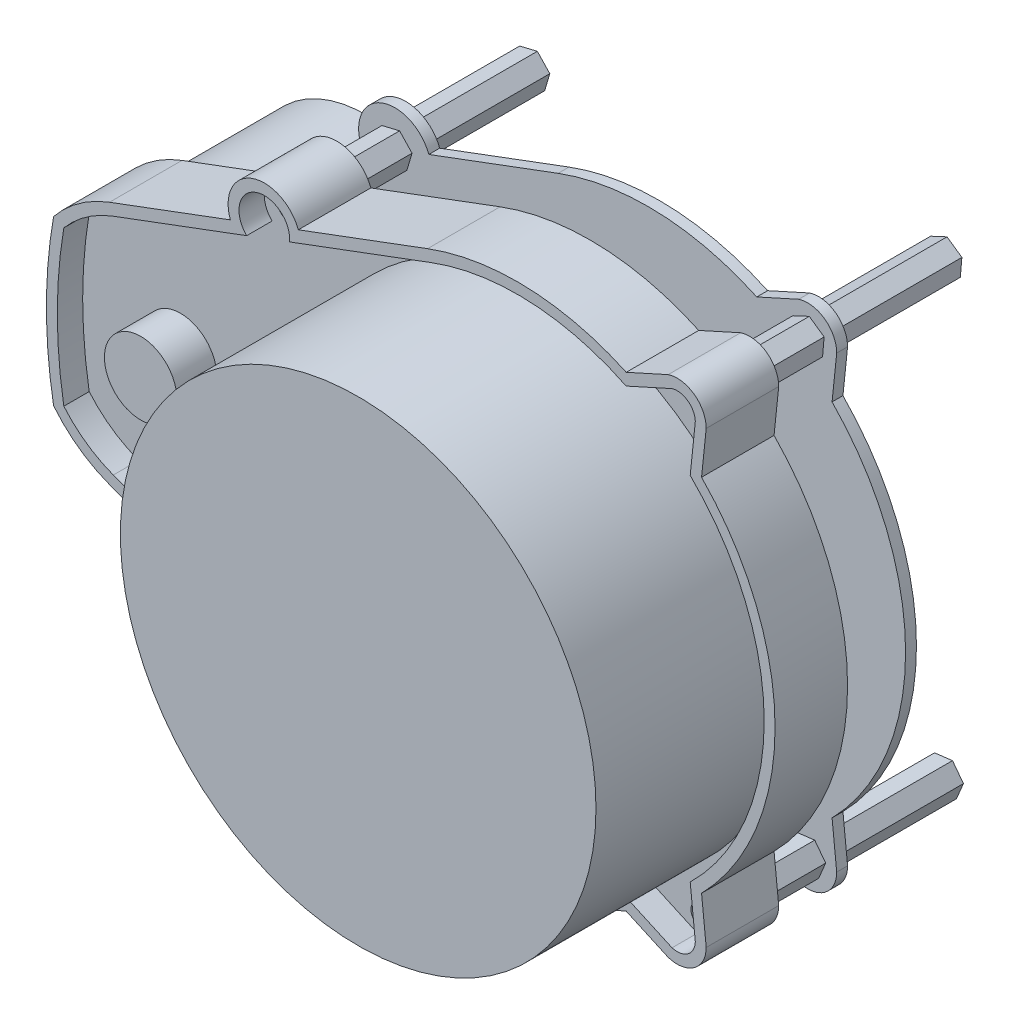
SolidWorks part; units mm, degrees
ref_plane "Plan de face" through (0, 0, 0) normal (0, 0, 1) x (1, 0, 0)
ref_plane "Plan de dessus" through (0, 0, 0) normal (0, 1, 0) x (1, 0, 0)
ref_plane "Plan de droite" through (0, 0, 0) normal (1, 0, 0) x (0, 0, -1)
sketch "Esquisse1" plane through (0, 0, 0) normal (0, 0, 1) x (1, 0, 0)
  line L0 (-12.425, 33.2546) -> (-30.2572, 26.5919)
  line L1 (-56.3, 16.8615) -> (-56.3, -16.8615) construction
  line L2 (-50, 0) -> (0, 0) construction
  line L3 (-12.425, 33.2546) -> (-12.425, -33.2546) construction
  line L5 (-35, 25) -> (-34.9409, 24.8419) construction
  line L6 (-39.6247, 23.0919) -> (-56.3, 16.8615)
  line L7 (-33.4505, 25.3988) -> (-36.4314, 24.2851)
  line L8 (20.756, 34.8016) -> (14.974, 32.1874)
  line L9 (26, 31) -> (25.36, 24.8419)
  line L10 (-65, 0) -> (35.5, 0) construction
  line L11 (55, 0) -> (-55, 0) construction
  line L12 (-35, -25) -> (-34.9409, -24.8419) construction
  line L13 (26, -31) -> (25.36, -24.8419)
  line L14 (20.756, -34.8016) -> (14.974, -32.1874)
  line L15 (-33.4505, -25.3988) -> (-36.4314, -24.2851)
  line L16 (-39.6247, -23.0919) -> (-56.3, -16.8615)
  line L17 (-12.425, -33.2546) -> (-30.2572, -26.5919)
  arc A1 (25.36, -24.8419) -> (25.36, 24.8419) centre (0, 0) ccw
  arc A3 (-64.01, 11.3013) -> (-64.01, -11.3013) centre (0, 0) ccw
  arc A4 (-56.3, 16.8615) -> (-64.01, 11.3013) centre (-50, 0) ccw
  circle A5 centre (22, 31) radius 1.6
  circle A6 centre (-35, 25) radius 1.6
  arc A7 (-30.2572, 26.5919) -> (-39.6247, 23.0919) centre (-34.9409, 24.8419) ccw
  arc A8 (26, 31) -> (20.756, 34.8016) centre (22, 31) ccw
  arc A9 (14.974, 32.1874) -> (-12.425, 33.2546) centre (0, 0) ccw
  arc A10 (14.974, -32.1874) -> (-12.425, -33.2546) centre (0, 0) cw
  arc A11 (26, -31) -> (20.756, -34.8016) centre (22, -31) cw
  arc A12 (-30.2572, -26.5919) -> (-39.6247, -23.0919) centre (-34.9409, -24.8419) cw
  circle A13 centre (-35, -25) radius 1.6
  circle A14 centre (22, -31) radius 1.6
  arc A15 (-56.3, -16.8615) -> (-64.01, -11.3013) centre (-50, 0) cw
  point P28 (-12.425, 0)
  point P29 (-56.3, 0)
  dimension "D1" = 71
  dimension "D4" = 130
  dimension "D6" = 3.2
  dimension "D10" = 10
  dimension "D11" = 8
  dimension "D3" = 50
  dimension "D5" = 31
  dimension "D7" = 22
  dimension "D8" = 35
  dimension "D9" = 25
extrude "Boss.-Extru.1" add sketch "Esquisse1" along normal blind 10 contours A15 L16 A12 L17 A10 L14 A11 L13 A1 L9 A8 L8 A9 L0 A7 L6 A4 A3 A13 A5 A6 A14 region at (-11.1105, 0, 0)
sketch "Esquisse2" plane through (0, 0, 10) normal (0, 0, 1) x (1, 0, 0)
  circle A0 centre (0, 0) radius 32.8
  dimension "D1" = 65.6
extrude "Boss.-Extru.2" add sketch "Esquisse2" along normal blind 22
sketch "Esquisse3" plane through (0, 0, 10) normal (0, 0, 1) x (1, 0, 0)
  line L16 (-55.775, -15.4564) -> (-37.3782, -22.33)
  line L17 (14.9568, -30.5335) -> (21.2911, -33.3974)
  line L18 (24.4991, -31.0687) -> (23.7942, -24.2866)
  line L19 (23.7942, 24.2866) -> (24.4991, 31.0687)
  line L20 (21.2911, 33.3974) -> (14.9568, 30.5335)
  line L21 (-11.9, 31.8495) -> (-31.4537, 24.5436)
  line L22 (-55.775, -15.4564) -> (-37.3782, -22.33)
  line L23 (14.9568, -30.5335) -> (21.2911, -33.3974)
  line L24 (24.4991, -31.0687) -> (23.7942, -24.2866)
  line L25 (23.7942, 24.2866) -> (24.4991, 31.0687)
  line L26 (21.2911, 33.3974) -> (14.9568, 30.5335)
  line L27 (-11.9, 31.8495) -> (-31.4537, 24.5436)
  line L28 (-31.4537, -24.5436) -> (-11.9, -31.8495)
  line L29 (-31.4537, -24.5436) -> (-11.9, -31.8495)
  line L30 (-37.3782, 22.33) -> (-55.775, 15.4564)
  line L31 (-37.3782, 22.33) -> (-55.775, 15.4564)
  arc A20 (-62.6, -10.6532) -> (-55.775, -15.4564) centre (-50, 0) ccw
  arc A21 (-11.9, -31.8495) -> (14.9568, -30.5335) centre (0, 0) ccw
  arc A22 (23.7942, -24.2866) -> (23.7942, 24.2866) centre (0, 0) ccw
  arc A23 (14.9568, 30.5335) -> (-11.9, 31.8495) centre (0, 0) ccw
  arc A24 (-55.775, 15.4564) -> (-62.6, 10.6532) centre (-50, 0) ccw
  arc A25 (-62.6, 10.6532) -> (-62.6, -10.6532) centre (0, 0) ccw
  arc A26 (-62.6, -10.6532) -> (-55.775, -15.4564) centre (-50, 0) ccw
  arc A27 (-11.9, -31.8495) -> (14.9568, -30.5335) centre (0, 0) ccw
  arc A28 (23.7942, -24.2866) -> (23.7942, 24.2866) centre (0, 0) ccw
  arc A29 (14.9568, 30.5335) -> (-11.9, 31.8495) centre (0, 0) ccw
  arc A30 (-55.775, 15.4564) -> (-62.6, 10.6532) centre (-50, 0) ccw
  arc A31 (-62.6, 10.6532) -> (-62.6, -10.6532) centre (0, 0) ccw
  arc A32 (-37.3782, -22.33) -> (-31.4537, -24.5436) centre (-34.9409, -24.8419) ccw
  arc A33 (-37.3782, -22.33) -> (-31.4537, -24.5436) centre (-34.9409, -24.8419) ccw
  arc A34 (21.2911, -33.3974) -> (24.4991, -31.0687) centre (22, -31) ccw
  arc A35 (21.2911, -33.3974) -> (24.4991, -31.0687) centre (22, -31) ccw
  arc A36 (24.4991, 31.0687) -> (21.2911, 33.3974) centre (22, 31) ccw
  arc A37 (24.4991, 31.0687) -> (21.2911, 33.3974) centre (22, 31) ccw
  arc A38 (-31.4537, 24.5436) -> (-37.3782, 22.33) centre (-34.9409, 24.8419) ccw
  arc A39 (-31.4537, 24.5436) -> (-37.3782, 22.33) centre (-34.9409, 24.8419) ccw
  dimension "D1" = 1.5
extrude "Enlèv. mat.-Extru.1" cut sketch "Esquisse3" against normal blind 3.5
sketch "Esquisse4" plane through (0, 0, 10) normal (0, 0, -1) x (-1, 0, 0)
  circle A1 centre (0, 0) radius 32.8
  circle A2 centre (0, 0) radius 32.8
  dimension "D1" = 0
extrude "Boss.-Extru.3" add sketch "Esquisse4" along normal up to next
sketch "Esquisse5" plane through (0, 0, 0) normal (0, 0, -1) x (-1, 0, 0)
  circle A0 centre (50, 0) radius 16
  dimension "D2" = 32
  dimension "D1" = 50
extrude "Boss.-Extru.4" add sketch "Esquisse5" along normal blind 19
sketch "Esquisse6" plane through (0, 0, 0) normal (0, 0, -1) x (-1, 0, 0)
  line L1 (-20.4892, -29.0081) -> (-22.9696, -28.6957)
  line L2 (-22.9696, -28.6957) -> (-24.4804, -30.6876)
  line L3 (-24.4804, -30.6876) -> (-23.5108, -32.9919)
  line L4 (-23.5108, -32.9919) -> (-21.0304, -33.3043)
  line L5 (-21.0304, -33.3043) -> (-19.5196, -31.3124)
  line L6 (-19.5196, -31.3124) -> (-20.4892, -29.0081)
  line L7 (36.0868, -22.7486) -> (33.5937, -22.9331)
  line L8 (33.5937, -22.9331) -> (32.5068, -25.1845)
  line L9 (32.5068, -25.1845) -> (33.9132, -27.2514)
  line L10 (33.9132, -27.2514) -> (36.4063, -27.0669)
  line L11 (36.4063, -27.0669) -> (37.4932, -24.8155)
  line L12 (37.4932, -24.8155) -> (36.0868, -22.7486)
  line L13 (36.7203, 26.814) -> (34.2892, 27.3968)
  line L14 (34.2892, 27.3968) -> (32.5689, 25.5828)
  line L15 (32.5689, 25.5828) -> (33.2797, 23.186)
  line L16 (33.2797, 23.186) -> (35.7108, 22.6032)
  line L17 (35.7108, 22.6032) -> (37.4311, 24.4172)
  line L18 (37.4311, 24.4172) -> (36.7203, 26.814)
  line L19 (-19.9522, 32.434) -> (-22.218, 33.4905)
  line L20 (-22.218, 33.4905) -> (-24.2658, 32.0565)
  line L21 (-24.2658, 32.0565) -> (-24.0478, 29.566)
  line L22 (-24.0478, 29.566) -> (-21.782, 28.5095)
  line L23 (-21.782, 28.5095) -> (-19.7342, 29.9435)
  line L24 (-19.7342, 29.9435) -> (-19.9522, 32.434)
  circle A0 centre (-22, -31) radius 2.1651 construction
  circle A1 centre (35, -25) radius 2.1651 construction
  circle A2 centre (35, 25) radius 2.1651 construction
  circle A3 centre (-22, 31) radius 2.1651 construction
  circle A4 centre (35, -25) radius 1
  circle A5 centre (35, 25) radius 1
  circle A6 centre (-22, 31) radius 1
  circle A7 centre (-22, -31) radius 1
  dimension "D2" = 2
  dimension "D1" = 5
extrude "Boss.-Extru.5" add sketch "Esquisse6" along normal blind 27
ref_plane "Plan1" through (0, 0, -8) normal (0, 0, -1) x (-1, 0, 0)
sketch "Esquisse7" plane through (0, 0, -8) normal (0, 0, -1) x (-1, 0, 0)
  line L0 (50, 0) -> (80, 0) construction
  line L8 (56.3, 16.8615) -> (39.6247, 23.0919)
  line L9 (30.2572, 26.5919) -> (12.425, 33.2546)
  line L10 (-14.974, 32.1874) -> (-20.756, 34.8016)
  line L11 (-26, 31) -> (-25.36, 24.8419)
  line L12 (-25.36, -24.8419) -> (-26, -31)
  line L13 (-20.756, -34.8016) -> (-14.974, -32.1874)
  line L14 (12.425, -33.2546) -> (30.2572, -26.5919)
  line L15 (39.6247, -23.0919) -> (56.3, -16.8615)
  line L17 (30.2572, 26.5919) -> (12.425, 33.2546)
  line L18 (-14.974, 32.1874) -> (-20.756, 34.8016)
  line L19 (-26, 31) -> (-25.36, 24.8419)
  line L20 (-25.36, -24.8419) -> (-26, -31)
  line L21 (-20.756, -34.8016) -> (-14.974, -32.1874)
  line L22 (12.425, -33.2546) -> (30.2572, -26.5919)
  arc A0 (39.6247, 23.0919) -> (39.6247, -23.0919) centre (80, 0) ccw
  arc A12 (64.69, 6.3407) -> (64.69, -6.3407) centre (50, 0) ccw
  arc A13 (64.69, 6.3407) -> (64.01, 11.3013) centre (0, 0) ccw
  arc A14 (64.01, 11.3013) -> (56.3, 16.8615) centre (50, 0) ccw
  arc A15 (39.6247, 23.0919) -> (30.2572, 26.5919) centre (34.9409, 24.8419) ccw
  arc A16 (12.425, 33.2546) -> (-14.974, 32.1874) centre (0, 0) ccw
  arc A17 (-20.756, 34.8016) -> (-26, 31) centre (-22, 31) ccw
  arc A18 (-25.36, 24.8419) -> (-25.36, -24.8419) centre (0, 0) ccw
  arc A19 (-26, -31) -> (-20.756, -34.8016) centre (-22, -31) ccw
  arc A20 (-14.974, -32.1874) -> (12.425, -33.2546) centre (0, 0) ccw
  arc A21 (30.2572, -26.5919) -> (39.6247, -23.0919) centre (34.9409, -24.8419) ccw
  arc A22 (56.3, -16.8615) -> (64.01, -11.3013) centre (50, 0) ccw
  arc A23 (64.01, -11.3013) -> (64.69, -6.3407) centre (0, 0) ccw
  arc A27 (39.6247, 23.0919) -> (30.2572, 26.5919) centre (34.9409, 24.8419) ccw
  arc A28 (12.425, 33.2546) -> (-14.974, 32.1874) centre (0, 0) ccw
  arc A29 (-20.756, 34.8016) -> (-26, 31) centre (-22, 31) ccw
  arc A30 (-25.36, 24.8419) -> (-25.36, -24.8419) centre (0, 0) ccw
  arc A31 (-26, -31) -> (-20.756, -34.8016) centre (-22, -31) ccw
  arc A32 (-14.974, -32.1874) -> (12.425, -33.2546) centre (0, 0) ccw
  arc A33 (30.2572, -26.5919) -> (39.6247, -23.0919) centre (34.9409, -24.8419) ccw
  dimension "D2" = 30
  dimension "D1" = 0
extrude "Boss.-Extru.6" add sketch "Esquisse7" along normal blind 1.5
sketch "Esquisse8" plane through (0, 0, 6.5) normal (0, 0, 1) x (1, 0, 0)
  circle A0 centre (-50, 0) radius 5
  dimension "D1" = 10
extrude "Boss.-Extru.7" add sketch "Esquisse8" along normal blind 5.5
